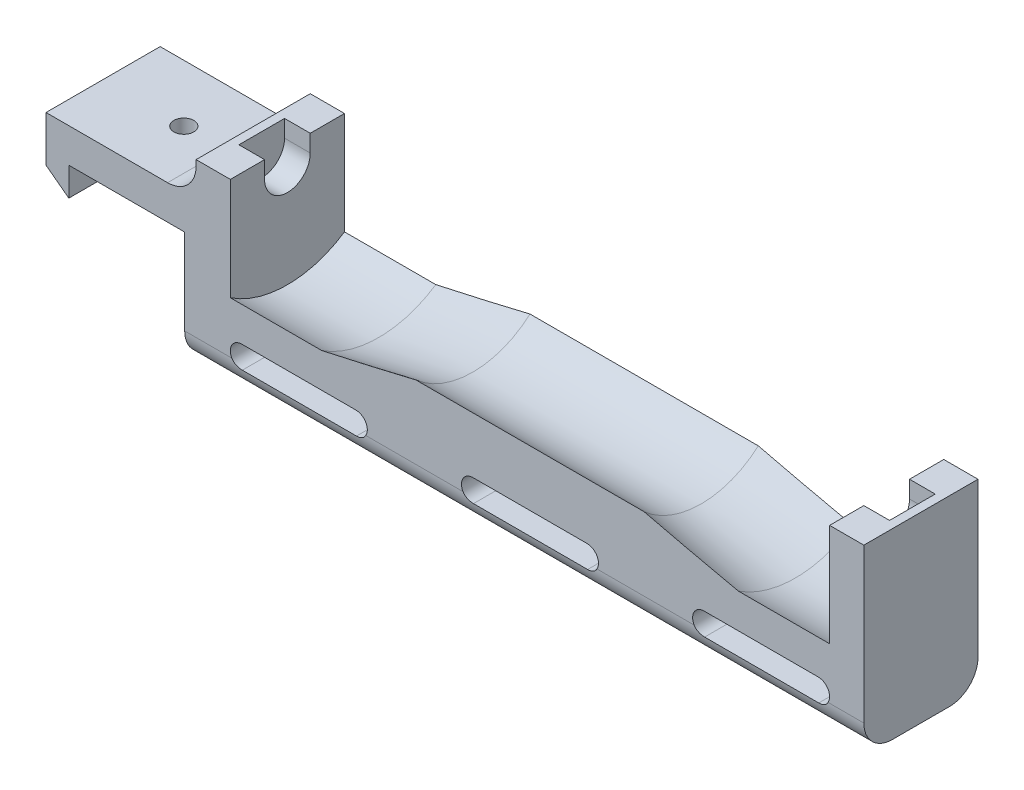
SolidWorks part; units mm, degrees
ref_plane "Plano frontal" through (0, 0, 0) normal (0, 0, 1) x (1, 0, 0)
ref_plane "Plano superior" through (0, 0, 0) normal (0, 1, 0) x (1, 0, 0)
ref_plane "Plano direito" through (0, 0, 0) normal (1, 0, 0) x (0, 0, -1)
sketch "Esboço1" plane through (0, 0, 0) normal (0, 0, 1) x (1, 0, 0)
  line L0 (0, 0) -> (4, -3)
  line L1 (4, -3) -> (4, 2)
  line L2 (4, 2) -> (24.3, 2)
  line L3 (24.3, 2) -> (24.3, -18)
  line L4 (34.3, -12) -> (54.3, -12) construction
  line L5 (24.3, -18) -> (143.3, -18)
  line L6 (143.3, -18) -> (143.3, 14)
  line L7 (143.3, 14) -> (137.3, 14)
  line L8 (137.3, 14) -> (137.3, 0)
  line L9 (137.3, 0) -> (32.3, 0)
  line L10 (32.3, 0) -> (32.3, 14)
  line L11 (32.3, 14) -> (26.3, 14)
  line L12 (26.3, 14) -> (26.3, 8)
  line L13 (26.3, 8) -> (0, 8)
  line L14 (0, 8) -> (0, 0)
  line L15 (34.3, -10) -> (54.3, -10)
  line L16 (34.3, -14) -> (54.3, -14)
  line L17 (74.8, -12) -> (94.8, -12) construction
  line L18 (74.8, -10) -> (94.8, -10)
  line L19 (74.8, -14) -> (94.8, -14)
  line L20 (115.3, -12) -> (135.3, -12) construction
  line L21 (115.3, -10) -> (135.3, -10)
  line L22 (115.3, -14) -> (135.3, -14)
  arc A0 (34.3, -10) -> (34.3, -14) centre (34.3, -12) ccw
  arc A1 (54.3, -14) -> (54.3, -10) centre (54.3, -12) ccw
  arc A2 (74.8, -10) -> (74.8, -14) centre (74.8, -12) ccw
  arc A3 (94.8, -14) -> (94.8, -10) centre (94.8, -12) ccw
  arc A4 (115.3, -10) -> (115.3, -14) centre (115.3, -12) ccw
  arc A5 (135.3, -14) -> (135.3, -10) centre (135.3, -12) ccw
  point P7 (44.3, -12)
  point P24 (84.8, -12)
  point P31 (125.3, -12)
  dimension "D11" = 2
  dimension "D1" = 105
  dimension "D2" = 6
  dimension "D3" = 2
  dimension "D4" = 6
  dimension "D5" = 20.3
  dimension "D6" = 20
  dimension "D7" = 18
  dimension "D8" = 14
  dimension "D9" = 4
  dimension "D10" = 5
  dimension "D12" = 6
  dimension "D13" = 10
  dimension "D14" = 20
  dimension "D16" = 8
  dimension "D17" = 3
  dimension "D15" = 3
extrude "Ressalto-extrusão1" add sketch "Esboço1" along normal mid plane 20
sketch "Esboço2" plane through (0, 0, 0) normal (0, 0, 1) x (1, 0, 0)
  line L0 (27.8, 11) -> (141.8, 11)
  line L3 (141.8, 11) -> (141.8, 7)
  line L4 (141.8, 7) -> (137.3, 7)
  line L5 (137.3, 7) -> (137.3, -7)
  line L6 (104.8, -4) -> (64.8, -4)
  line L7 (32.3, -7) -> (32.3, 7)
  line L8 (32.3, 7) -> (27.8, 7)
  line L9 (27.8, 7) -> (27.8, 11)
  line L10 (32.3, 14) -> (26.3, 14) construction
  line L13 (32.3, -7) -> (48.3, -7)
  line L16 (121.3, -7) -> (137.3, -7)
  line L17 (26.3, 14) -> (26.3, 8) construction
  line L18 (143.3, -18) -> (143.3, 14) construction
  line L19 (137.3, 14) -> (137.3, 0) construction
  line L20 (48.3, -7) -> (64.8, -4)
  line L21 (121.3, -7) -> (104.8, -4)
  line L22 (84.8, 11) -> (84.8, -7) construction
  dimension "D1" = 1.5
  dimension "D2" = 3
  dimension "D3" = 4
  dimension "D4" = 15
  dimension "D5" = 16
  dimension "D6" = 18
  dimension "D7" = 1.5
  dimension "D8" = 40
revolve "Corte-Revolução1" cut sketch "Esboço2" angle 360 about L0
sketch "Esboço4" plane through (32.3, 0, 0) normal (1, 0, 0) x (0, 0, -1)
  line L0 (2.6458, 14) -> (10, 14) construction
  line L1 (4, 11) -> (-4, 11)
  line L2 (4, 11) -> (4, 14)
  line L3 (4, 14) -> (-4, 14)
  line L4 (-4, 11) -> (-4, 14)
  arc A0 (-2.6458, 14) -> (2.6458, 14) centre (0, 11) ccw construction
extrude "Corte-extrusão1" cut sketch "Esboço4" against normal up to surface and the other way up to surface up to face at (27.8, 10.5, 0) other way up to face at (141.8, 10.5, 0)
fillet "Filete1" radius 5 2 edges at (83.8, -18, -10) (83.8, -18, 10)
sketch "Esboço7" plane through (0, 2, 0) normal (0, -1, 0) x (1, 0, 0)
  line L0 (4, 10) -> (24.3, 10) construction
  circle A0 centre (14.15, 0) radius 1.75
  point P5 (14.15, 10)
  dimension "D1" = 3.5
extrude "Corte-extrusão3" cut sketch "Esboço7" against normal blind 15
fillet "Filete2" radius 5 1 edges at (26.3, 8, 0)
